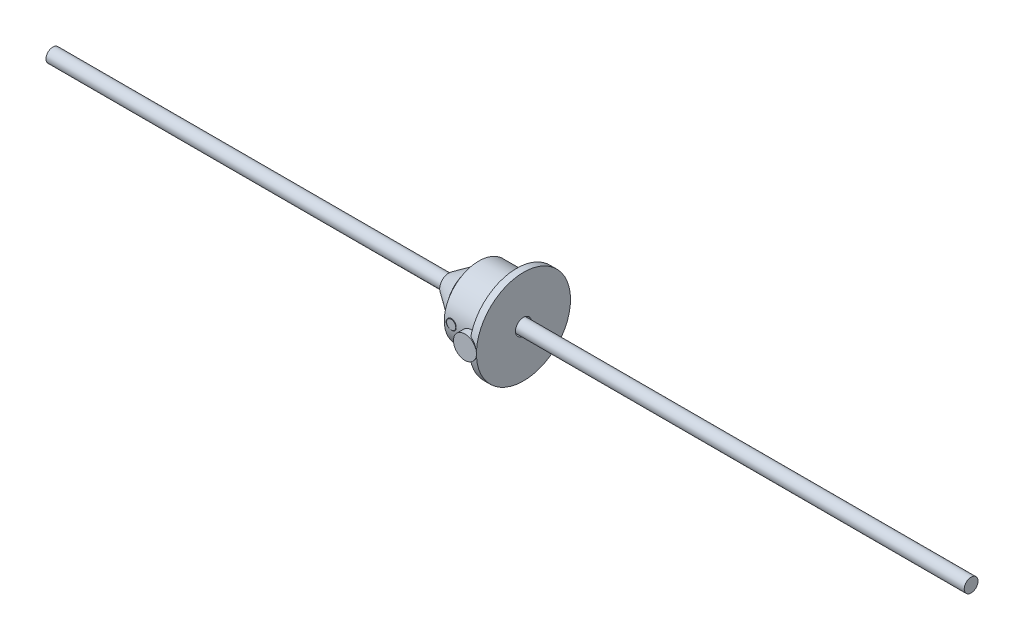
SolidWorks part; units mm, degrees
other "RD S Gear Inner"
other "RD S Gear Outer"
other "RD L Gear Left"
other "RD L Gear Right"
other "RD Ring Gear"
other "RD Pinion"
other "RD S Gear Inner"
ref_plane "Front Plane" through (0, 0, 0) normal (0, 0, 1) x (1, 0, 0)
ref_plane "Top Plane" through (0, 0, 0) normal (0, 1, 0) x (1, 0, 0)
ref_plane "Right Plane" through (0, 0, 0) normal (1, 0, 0) x (0, 0, -1)
sketch "Top View Layout" plane through (0, 0, 0) normal (0, 1, 0) x (1, 0, 0)
  line L0 (-100, 125) -> (100, 125)
  line L1 (0, 125) -> (0, -125)
  line L2 (-100, -125) -> (100, -125)
  line L3 (0, -15) -> (35, -15) construction
  line L4 (35, -15) -> (35, -125) construction
  line L5 (2.5, 114.75) -> (2.5, 135.25) construction
  line L6 (-2.5, 114.75) -> (2.5, 114.75) construction
  line L7 (-8.75, 127) -> (-2.75, 127) construction
  line L8 (-2.5, 114.75) -> (2.5, 114.75) construction
  line L9 (-2.5, 114.75) -> (-2.5, 116.25) construction
  line L10 (-2.5, 116.25) -> (2.5, 116.25) construction
  line L11 (2.5, 114.75) -> (2.5, 116.25) construction
  line L12 (2.5, 135.25) -> (1, 135.25) construction
  line L13 (2.5, 135.25) -> (2.5, 114.75) construction
  line L14 (2.5, 114.75) -> (1, 114.75) construction
  line L15 (1, 135.25) -> (1, 114.75) construction
  line L16 (-4.25, 128.5) -> (-2.75, 128.5) construction
  line L17 (-4.25, 128.5) -> (-4.25, 121.5) construction
  line L18 (-4.25, 121.5) -> (-2.75, 121.5) construction
  line L19 (-2.75, 128.5) -> (-2.75, 121.5) construction
  line L20 (-4.25, 128.5) -> (-2.75, 121.5) construction
  line L21 (-4.25, 121.5) -> (-2.75, 128.5) construction
  line L22 (-8.75, 128.5) -> (-7.25, 128.5) construction
  line L23 (-8.75, 128.5) -> (-8.75, 121.5) construction
  line L24 (-8.75, 121.5) -> (-7.25, 121.5) construction
  line L25 (-7.25, 128.5) -> (-7.25, 121.5) construction
  line L26 (-8.75, 128.5) -> (-7.25, 121.5) construction
  line L27 (-8.75, 121.5) -> (-7.25, 128.5) construction
  line L28 (-8.75, 123) -> (-2.75, 123) construction
  line L29 (-5.75, 123) -> (-5.75, 120.2863) construction
  line L30 (-5.75, 127) -> (-5.75, 129.2691) construction
  point P8 (0, 114.75)
  point P9 (0, 0)
  point P11 (2.5, 125)
  point P16 (2.5, 125)
  point P19 (0, 114.75)
  point P23 (-3.5, 125)
  point P28 (-8, 125)
  dimension "D1" = 250
  dimension "D2" = 200
  dimension "D3" = 35
  dimension "D4" = 15
  dimension "D5" = 5
  dimension "D6" = 20.5
  dimension "D7" = 1.5
  dimension "D8" = 1.5
  dimension "D9" = 1.5
  dimension "D10" = 7
  dimension "D11" = 3.5
  dimension "D12" = 8
  dimension "D13" = 1.5
  dimension "D14" = 1.5
ref_plane "Left" through (100, 0, 0) normal (-1, 0, 0) x (0, 0, 1)
ref_plane "Right" through (-100, 0, 0) normal (-1, 0, 0) x (0, 0, 1)
sketch "Left Wheels" plane through (100, 0, 0) normal (-1, 0, 0) x (0, 0, 1)
  circle A0 centre (125, 0) radius 25
  circle A1 centre (-125, 0) radius 25
  point P4 (0, 0)
  point P6 (0, 0)
  point P8 (0, 0)
  point P9 (0, 0)
  point P10 (0, 0)
  dimension "D1" = 50
  dimension "D2" = 50
sketch "Right Wheels" plane through (-100, 0, 0) normal (-1, 0, 0) x (0, 0, 1)
  circle A0 centre (-125, 0) radius 25 construction
  circle A1 centre (125, 0) radius 25 construction
  circle A2 centre (-125, 0) radius 25
  circle A3 centre (125, 0) radius 25
  point P6 (0, 0)
ref_plane "Rear Differential Pinion Plane" through (0, 0, -114.75) normal (0, 0, 1) x (1, 0, 0)
sketch "Rear Differential Pinion Profile" plane through (0, 0, -114.75) normal (0, 0, 1) x (1, 0, 0)
  circle A0 centre (0, 0) radius 2.5
ref_plane "Rear Differential Ring Gear Plane" through (2.5, 0, 0) normal (1, 0, 0) x (0, 0, -1)
ref_plane "Rear Axle" through (0, 0, -125) normal (0, 0, 1) x (1, 0, 0)
sketch "Rear Differential Ring Gear Profile" plane through (2.5, 0, 0) normal (1, 0, 0) x (0, 0, -1)
  line L0 (114.75, 0) -> (135.25, 0) construction
  circle A0 centre (125, 0) radius 10.25
extrude "Rear Differential Pinion" add sketch "Rear Differential Pinion Profile" against normal blind 1.5 contours A0
extrude "Rear Differential Ring Gear" add sketch "Rear Differential Ring Gear Profile" against normal blind 1.5 separate body contours A0
ref_plane "RD Inner L Gear Plane" through (-2.75, 0, 0) normal (1, 0, 0) x (0, 0, -1)
ref_plane "RD Outer L Gear Plane" through (-8.75, 0, 0) normal (1, 0, 0) x (0, 0, -1)
sketch "RD Inner L Gear Profile" plane through (-2.75, 0, 0) normal (1, 0, 0) x (0, 0, -1)
  circle A0 centre (125, 0) radius 3.5
  point P2 (0, 0)
sketch "RD Outer L Gear Profile" plane through (-8.75, 0, 0) normal (1, 0, 0) x (0, 0, -1)
  line L0 (128.5, 0) -> (121.5, 0) construction
  circle A0 centre (125, 0) radius 3.5
ref_plane "RD Inner S Gear Plane" through (0, 0, -121.5) normal (0, 0, 1) x (1, 0, 0)
ref_plane "RD Outer S Gear Plane" through (0, 0, -128.5) normal (0, 0, 1) x (1, 0, 0)
sketch "RD Inner S Gear Profile" plane through (0, 0, -121.5) normal (0, 0, 1) x (1, 0, 0)
  line L0 (-8.75, 0) -> (-7.25, 0) construction
  circle A0 centre (-5.75, 0) radius 3
  point P3 (0, 0)
sketch "RD Outer S Gear Profile" plane through (0, 0, -128.5) normal (0, 0, 1) x (1, 0, 0)
  line L0 (-8.75, 0) -> (-7.25, 0) construction
  circle A2 centre (-5.75, 0) radius 3
  point P2 (0, 0)
extrude "RD Outer L Gear Extrude" add sketch "RD Outer L Gear Profile" along normal blind 1.5 separate body contours A0
extrude "RD Inner L Gear Extrude" add sketch "RD Inner L Gear Profile" against normal blind 1.5 separate body contours A0
extrude "RD Outer S Gear Extrude" add sketch "RD Outer S Gear Profile" along normal blind 1.5 separate body contours A2
extrude "RD Inner S Gear Extrude" add sketch "RD Inner S Gear Profile" against normal blind 1.5 separate body contours A0
sketch "RD Ring Gear Case Profile" plane through (1, 0, 0) normal (-1, 0, 0) x (0, 0, 1)
  line L0 (-121.5, 3.2113) -> (-121.5, -3.2113)
  line L1 (-128.5, 3.2113) -> (-128.5, -3.2113)
  line L2 (-121.5, 6.6332) -> (-121.5, 3.2113) construction
  line L3 (-128.5, 6.6332) -> (-128.5, 3.2113) construction
  line L4 (-121.5, -3.2113) -> (-121.5, -6.6332) construction
  line L5 (-128.5, -3.2113) -> (-128.5, -6.6332) construction
  circle A0 centre (-125, 0) radius 7.5
  arc A1 (-121.5, 3.2113) -> (-128.5, 3.2113) centre (-125, 0) ccw
  arc A2 (-121.5, -3.2113) -> (-121.5, 3.2113) centre (-125, 0) ccw construction
  arc A3 (-128.5, 3.2113) -> (-128.5, -3.2113) centre (-125, 0) ccw construction
  arc A4 (-128.5, -3.2113) -> (-121.5, -3.2113) centre (-125, 0) ccw
  point P7 (-121.5, 0)
  dimension "D1" = 15
  dimension "D2" = 9.5
extrude "RD Ring Gear Case " add sketch "RD Ring Gear Case Profile" along normal blind 8.25
sketch "Sketch11" plane through (-7.25, 0, 0) normal (-1, 0, 0) x (0, 0, 1)
  circle A0 centre (-125, 0) radius 5.5
  circle A1 centre (-125, 0) radius 4.75
  arc A2 (-121.5, 3.2113) -> (-128.5, 3.2113) centre (-125, 0) ccw construction
  dimension "D1" = 11
extrude "Boss-Extrude8" add sketch "Sketch11" along normal up to vertex up to point (-8.75, 0, -128.5)
fillet "Fillet1" radius 2 1 edges at (-7.25, 0, -119.5)
sketch "Sketch12" plane through (0, 0, -125) normal (0, 0, 1) x (1, 0, 0)
  line L0 (-8.75, 0) -> (-13.75, 0) construction
  line L1 (-8.75, 0) -> (-7.25, 0) construction
  line L2 (-8.75, 0) -> (-7.25, 0) construction
  line L3 (-100, 0) -> (100, 0) construction
  line L4 (-100, 0) -> (100, 0) construction
  line L5 (-8.75, 5.5) -> (-8.75, -5.5) construction
  line L6 (-13.75, 0) -> (-13.75, 2)
  line L7 (-13.75, 2) -> (-8.75, 5.5)
  line L8 (-13.75, 0) -> (-8.75, 0)
  line L9 (-8.75, 0) -> (-8.75, 5.5)
  point P15 (-13.75, 1)
  dimension "D1" = 5
  dimension "D2" = 2
revolve "Revolve1" add sketch "Sketch12" angle 360 about L0
sketch "Sketch13" plane through (2.5, 0, 0) normal (1, 0, 0) x (0, 0, -1)
  circle A0 centre (125, 0) radius 1.75
  dimension "D1" = 3.5
extrude "Cut-Extrude1" cut sketch "Sketch13" against normal through all
sketch "Sketch14" plane through (0, 0, -121.5) normal (0, 0, 1) x (1, 0, 0)
  circle A0 centre (-5.75, 0) radius 1
  dimension "D1" = 2
extrude "Boss-Extrude9" add sketch "Sketch14" along normal blind 4
sketch "Sketch15" plane through (0, 0, -121.5) normal (0, 0, 1) x (1, 0, 0)
  circle A0 centre (-5.75, 0) radius 1.1
  dimension "D1" = 2.2
extrude "Cut-Extrude2" cut sketch "Sketch15" against normal through all both and the other way through all
extrude "Boss-Extrude10" add sketch "Sketch14<2>" against normal blind 4 from surface starting at face at (-2.75, 0, -128.5)
sketch "Sketch14<2>" plane through (0, 0, -121.5) normal (0, 0, 1) x (1, 0, 0) same geometry as "Sketch14"
sketch "Sketch16" plane through (-8.75, 0, 0) normal (-1, 0, 0) x (0, 0, 1)
  circle A0 centre (-125, 0) radius 1.5
  dimension "D1" = 3
extrude "Boss-Extrude11" add sketch "Sketch16" along normal up to vertex (91.25 mm away) up to point (-100, 0, -125)
sketch "Sketch17" plane through (-2.75, 0, 0) normal (1, 0, 0) x (0, 0, -1)
  circle A0 centre (125, 0) radius 1.5 construction
  circle A1 centre (125, 0) radius 1.5
extrude "Boss-Extrude12" add sketch "Sketch17" along normal up to vertex (102.75 mm away) up to point (100, 0, -125)
